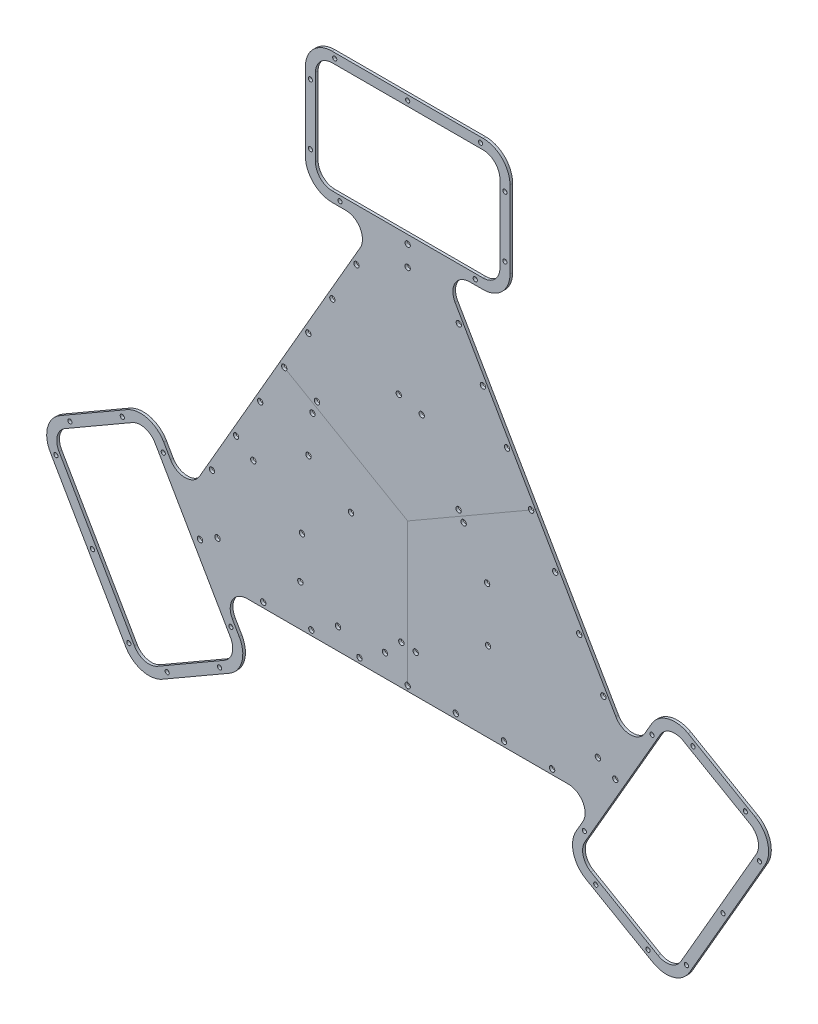
SolidWorks part; units mm, degrees
material "6061 Alloy"
ref_plane "Front Plane" through (0, 0, 0) normal (0, 0, 1) x (1, 0, 0)
ref_plane "Top Plane" through (0, 0, 0) normal (0, 1, 0) x (1, 0, 0)
ref_plane "Right Plane" through (0, 0, 0) normal (1, 0, 0) x (0, 0, -1)
sketch "Master" plane through (0, 0, 0) normal (0, 0, 1) x (1, 0, 0)
  line L0 (0, 0) -> (-128.1513, -73.9882) construction
  line L1 (0, 175.9764) -> (-152.4, -87.9882) construction
  line L2 (-152.4, -87.9882) -> (152.4, -87.9882) construction
  line L3 (152.4, -87.9882) -> (0, 175.9764) construction
  line L4 (0, 0) -> (128.1513, -73.9882) construction
  line L5 (0, 0) -> (0, 147.9764) construction
  line L7 (128.1513, -73.9882) -> (152.4, -87.9882) construction
  line L8 (-128.1513, -73.9882) -> (-152.4, -87.9882) construction
  line L10 (0, 147.9764) -> (0, 175.9764) construction
  line L16 (-16.1658, 147.9764) -> (16.1658, 147.9764)
  line L17 (16.1658, 147.9764) -> (136.2342, -59.9882)
  line L18 (-16.1658, 147.9764) -> (-136.2342, -59.9882)
  line L19 (136.2342, -59.9882) -> (128.1513, -73.9882)
  line L23 (128.1513, -73.9882) -> (120.0684, -87.9882)
  line L24 (120.0684, -87.9882) -> (-120.0684, -87.9882)
  line L25 (-120.0684, -87.9882) -> (-128.1513, -73.9882)
  line L29 (-128.1513, -73.9882) -> (-136.2342, -59.9882)
  circle A0 centre (0, 0) radius 175.9764 construction
  circle A1 centre (-123.8212, -71.4882) radius 5 construction
  circle A2 centre (-123.8212, -71.4882) radius 1.6 construction
  circle A3 centre (0, 142.9764) radius 5 construction
  circle A4 centre (123.8212, -71.4882) radius 5 construction
  circle A5 centre (123.8212, -71.4882) radius 1.6 construction
  circle A6 centre (0, 142.9764) radius 1.6 construction
  circle A11 centre (0, 130.9764) radius 5 construction
  circle A12 centre (0, 130.9764) radius 1.6 construction
  circle A13 centre (113.4289, -65.4882) radius 5 construction
  circle A14 centre (113.4289, -65.4882) radius 1.6 construction
  circle A15 centre (-113.4289, -65.4882) radius 5 construction
  circle A16 centre (-113.4289, -65.4882) radius 1.6 construction
  dimension "D6" = 3.2
  dimension "D5" = 10
  dimension "D3" = 304.8
  dimension "D7" = 12
  dimension "D8" = 12
  dimension "D9" = 12
  dimension "D1" = 28
extrude "Boss-Extrude2" add sketch "Master" along normal blind 1.6
ref_plane "Left Wheel Axle" through (0, 0, 0) normal (-0.5, -0.866, 0) x (0.866, -0.5, 0)
ref_plane "Right Wheel Axle" through (0, 0, 0) normal (-0.5, 0.866, 0) x (-0.866, -0.5, 0)
ref_plane "Rear Wheel Axle" through (0, 0, 0) normal (1, 0, 0) x (0, 1, 0)
ref_axis "Vertical center axis" through (0, 0, -238.9779) along (0, 0, 1)
sketch "Sketch2" plane through (0, 0, 0) normal (0, 0, 1) x (1, 0, 0)
  line L0 (0, 0) -> (0, 147.9764) construction
  line L1 (-55, 214.0964) -> (-55, 220.0964) construction
  line L2 (-55, 214.0964) -> (55, 214.0964)
  line L3 (-55, 214.0964) -> (-55, 147.9764)
  line L4 (-55, 147.9764) -> (55, 147.9764)
  line L5 (55, 214.0964) -> (55, 147.9764)
  line L6 (-55, 214.0964) -> (55, 147.9764) construction
  line L7 (-55, 147.9764) -> (55, 214.0964) construction
  line L8 (-61, 220.0964) -> (61, 220.0964)
  line L9 (-61, 220.0964) -> (-61, 141.9764)
  line L10 (-61, 141.9764) -> (61, 141.9764)
  line L11 (61, 220.0964) -> (61, 141.9764)
  line L12 (-61, 220.0964) -> (61, 141.9764) construction
  line L13 (-61, 141.9764) -> (61, 220.0964) construction
  line L14 (-55, 214.0964) -> (-61, 214.0964) construction
  line L15 (16.1658, 147.9764) -> (-16.1658, 147.9764) construction
  point P0 (0, 147.9764)
  point P3 (0, 181.0364)
  point P16 (0, 181.0364)
  dimension "D1" = 6
  dimension "D2" = 66.12
  dimension "D3" = 110
extrude "Wheel bumpers" add sketch "Sketch2" along normal up to surface (1.6 mm away) up to face at (0, 0, 1.6)
sketch "Sketch3" plane through (0, 0, 1.6) normal (0, 0, 1) x (1, 0, 0)
  line L0 (0, 220.0964) -> (0, 214.0964) construction
  line L1 (-61, 220.0964) -> (61, 220.0964) construction
  line L2 (-55, 214.0964) -> (55, 214.0964) construction
  line L3 (0, 217.0964) -> (29, 217.0964) construction
  line L4 (61, 220.0964) -> (61, 141.9764) construction
  line L5 (0, 217.0964) -> (-29, 217.0964) construction
  line L6 (-61, 141.9764) -> (-61, 220.0964) construction
  line L7 (-61, 181.0364) -> (-55, 181.0364) construction
  line L8 (-55, 147.9764) -> (-55, 214.0964) construction
  line L9 (55, 181.0364) -> (61, 181.0364) construction
  line L10 (55, 214.0964) -> (55, 147.9764) construction
  line L11 (58, 181.0364) -> (58, 144.9764) construction
  line L13 (58, 181.0364) -> (58, 217.0964) construction
  line L14 (-58, 181.0364) -> (-58, 217.0964) construction
  line L15 (-58, 181.0364) -> (-58, 144.9764) construction
  line L17 (-19.6299, 141.9764) -> (-19.6299, 147.9764) construction
  line L19 (19.6299, 141.9764) -> (19.6299, 147.9764) construction
  line L20 (55, 147.9764) -> (-55, 147.9764) construction
  line L21 (-19.6299, 141.9764) -> (19.6299, 141.9764) construction
  line L22 (-19.6299, 144.9764) -> (-61, 144.9764) construction
  line L23 (19.6299, 144.9764) -> (61, 144.9764) construction
  line L24 (-29, 217.0964) -> (-58, 217.0964) construction
  line L25 (29, 217.0964) -> (58, 217.0964) construction
  circle A0 centre (43.5, 217.0964) radius 1.25
  circle A1 centre (0, 217.0964) radius 1.25
  circle A2 centre (-43.5, 217.0964) radius 1.25
  circle A3 centre (-58, 199.0664) radius 1.25
  circle A4 centre (-58, 163.0064) radius 1.25
  circle A9 centre (58, 199.0664) radius 1.25
  circle A10 centre (58, 163.0064) radius 1.25
  circle A11 centre (-40.315, 144.9764) radius 1.25
  circle A12 centre (40.315, 144.9764) radius 1.25
  point P7 (43.5, 217.0964)
  point P27 (58, 163.0064)
  point P28 (58, 199.0664)
  point P34 (-58, 199.0664)
  point P35 (-58, 163.0064)
  point P66 (-43.5, 217.0964)
  dimension "D1" = 2.5
extrude "Bumper mounting holes" cut sketch "Sketch3" against normal up to next
fillet "Bumper outer fillets" radius 16 4 edges at (-61, 141.9764, 0.8) (-61, 220.0964, 0.8) (61, 220.0964, 0.8) (61, 141.9764, 0.8)
fillet "Bumper inner fillets" radius 10 4 edges at (55, 214.0964, 0.8) (55, 147.9764, 0.8) (-55, 147.9764, 0.8) (-55, 214.0964, 0.8)
pattern_circular "CirPattern3" count 3 every 120 about axis through (0, 0, -238.9779) along (0, 0, 1) of "Wheel bumpers", "Bumper mounting holes", "Bumper outer fillets", "Bumper inner fillets"
fillet "Bumper pocket fillets" radius 10 6 edges at (-19.6299, 141.9764, 0.8) (19.6299, 141.9764, 0.8) (132.7701, -53.9882, 0.8) (113.1402, -87.9882, 0.8) (-132.7701, -53.9882, 0.8) (-113.1402, -87.9882, 0.8)
sketch "Motor mounting holes" plane through (0, 0, 0) normal (0, 0, 1) x (1, 0, 0)
  circle A0 centre (0, 142.9764) radius 1.6
  circle A1 centre (0, 130.9764) radius 1.6
  circle A2 centre (-113.4289, -65.4882) radius 1.6
  circle A3 centre (-123.8212, -71.4882) radius 1.6
  circle A4 centre (113.4289, -65.4882) radius 1.6
  circle A5 centre (123.8212, -71.4882) radius 1.6
  dimension "D1" = 3.2
extrude "Motors" cut sketch "Motor mounting holes" along normal up to next
sketch "Sketch1" plane through (0, 0, 1.6) normal (0, 0, 1) x (1, 0, 0)
  circle A0 centre (-41.5385, -75.2533) radius 1.75 construction
  circle A2 centre (-13.5218, -74.7795) radius 1.75 construction
  circle A3 centre (-13.5218, -74.7795) radius 1.75 construction
  circle A4 centre (-41.5385, -75.2533) radius 1.75 construction
  circle A6 centre (-63.9798, -63.3837) radius 1.75 construction
  circle A7 centre (-63.9798, -63.3837) radius 1.75 construction
  circle A8 centre (-92.0288, -14.8014) radius 1.75 construction
  circle A9 centre (-92.0288, -14.8014) radius 1.75 construction
  circle A10 centre (-59.1198, 4.1986) radius 1.75 construction
  circle A11 centre (-59.1198, 4.1986) radius 1.75 construction
  circle A12 centre (-92.0288, -14.8014) radius 1.75 construction
  circle A13 centre (-59.1198, 4.1986) radius 1.75 construction
  circle A14 centre (-63.0385, -38.0142) radius 1.75 construction
  circle A15 centre (-63.0385, -38.0142) radius 1.75 construction
  circle A16 centre (-92.0288, -14.8014) radius 1.6
  circle A17 centre (-63.0385, -38.0142) radius 1.6
  circle A18 centre (-63.9798, -63.3837) radius 1.6
  circle A19 centre (-41.5385, -75.2533) radius 1.6
  circle A20 centre (-13.5218, -74.7795) radius 1.6
  circle A21 centre (-59.1198, 4.1986) radius 1.6
  dimension "D1" = 3.2
extrude "Extension board" cut sketch "Sketch1" against normal up to next
sketch "Sketch6" plane through (0, 0, 0) normal (0, 0, -1) x (-1, 0, 0)
  circle A0 centre (-86.1542, -84.9882) radius 1.6 construction
  circle A1 centre (-57.4361, -84.9882) radius 1.6 construction
  circle A2 centre (-28.7181, -84.9882) radius 1.6 construction
  circle A3 centre (0, -84.9882) radius 1.6 construction
  circle A4 centre (28.7181, -84.9882) radius 1.6 construction
  circle A5 centre (57.4361, -84.9882) radius 1.6 construction
  circle A6 centre (86.1542, -84.9882) radius 1.6 construction
  circle A7 centre (116.679, -32.1176) radius 1.6 construction
  circle A8 centre (102.32, -7.247) radius 1.6 construction
  circle A9 centre (87.9609, 17.6235) radius 1.6 construction
  circle A10 centre (73.6019, 42.4941) radius 1.6 construction
  circle A11 centre (59.2429, 67.3647) radius 1.6 construction
  circle A12 centre (44.8839, 92.2352) radius 1.6 construction
  circle A13 centre (30.5248, 117.1058) radius 1.6 construction
  circle A14 centre (-30.5248, 117.1058) radius 1.6 construction
  circle A15 centre (-44.8839, 92.2352) radius 1.6 construction
  circle A16 centre (-59.2429, 67.3647) radius 1.6 construction
  circle A17 centre (-73.6019, 42.4941) radius 1.6 construction
  circle A18 centre (-87.9609, 17.6235) radius 1.6 construction
  circle A19 centre (-102.32, -7.2471) radius 1.6 construction
  circle A20 centre (-116.679, -32.1176) radius 1.6 construction
  circle A21 centre (-86.1542, -84.9882) radius 1.6
  circle A22 centre (-57.4361, -84.9882) radius 1.6
  circle A23 centre (-28.7181, -84.9882) radius 1.6
  circle A24 centre (0, -84.9882) radius 1.6
  circle A25 centre (28.7181, -84.9882) radius 1.6
  circle A26 centre (57.4361, -84.9882) radius 1.6
  circle A27 centre (86.1542, -84.9882) radius 1.6
  circle A28 centre (116.679, -32.1176) radius 1.6
  circle A29 centre (102.32, -7.247) radius 1.6
  circle A30 centre (87.9609, 17.6235) radius 1.6
  circle A31 centre (73.6019, 42.4941) radius 1.6
  circle A32 centre (59.2429, 67.3647) radius 1.6
  circle A33 centre (44.8839, 92.2352) radius 1.6
  circle A34 centre (30.5248, 117.1058) radius 1.6
  circle A35 centre (-30.5248, 117.1058) radius 1.6
  circle A36 centre (-44.8839, 92.2352) radius 1.6
  circle A37 centre (-59.2429, 67.3647) radius 1.6
  circle A38 centre (-73.6019, 42.4941) radius 1.6
  circle A39 centre (-87.9609, 17.6235) radius 1.6
  circle A40 centre (-102.32, -7.2471) radius 1.6
  circle A41 centre (-116.679, -32.1176) radius 1.6
extrude "Side bumpers" cut sketch "Sketch6" against normal up to next
sketch "Sketch10" plane through (0, 0, 0) normal (0, 0, 1) x (1, 0, 0)
  line L0 (0, 0) -> (0, -87.9882)
  line L1 (-95.8197, -87.9882) -> (95.8197, -87.9882) construction
  line L2 (0, 0) -> (-76.2, 43.9941)
  line L3 (-28.2902, 126.9764) -> (-124.1098, -38.9882) construction
sketch "Sketch11" plane through (0, 0, 0) normal (0, 0, 1) x (1, 0, 0)
  circle A0 centre (-54.0477, 34.6134) radius 1.4 construction
  circle A1 centre (-56.7439, 27.2833) radius 1.4 construction
  circle A2 centre (-33.7439, -12.5538) radius 1.4 construction
  circle A3 centre (-3.7439, -64.5154) radius 1.4 construction
  circle A4 centre (4.8183, -65.3455) radius 1.4 construction
  circle A5 centre (47.9463, -40.4455) radius 1.4 construction
  circle A6 centre (47.3697, -8.4468) radius 1.4 construction
  circle A7 centre (33.3697, 15.8019) radius 1.4 construction
  circle A8 centre (30.3697, 20.9981) radius 1.4 construction
  circle A9 centre (-5.2905, 62.7634) radius 1.4 construction
  circle A10 centre (8.3697, 59.1032) radius 1.4 construction
  circle A11 centre (-54.0477, 34.6134) radius 1.4 construction
  circle A12 centre (-56.7439, 27.2833) radius 1.4 construction
  circle A13 centre (-33.7439, -12.5538) radius 1.4 construction
  circle A14 centre (-3.7439, -64.5154) radius 1.4 construction
  circle A15 centre (4.8183, -65.3455) radius 1.4 construction
  circle A16 centre (47.9463, -40.4455) radius 1.4 construction
  circle A17 centre (47.3697, -8.4468) radius 1.4 construction
  circle A18 centre (33.3697, 15.8019) radius 1.4 construction
  circle A19 centre (30.3697, 20.9981) radius 1.4 construction
  circle A20 centre (-5.2905, 62.7634) radius 1.4 construction
  circle A21 centre (8.3697, 59.1032) radius 1.4 construction
  circle A22 centre (-54.0477, 34.6134) radius 1.6
  circle A23 centre (-56.7439, 27.2833) radius 1.6
  circle A24 centre (-5.2905, 62.7634) radius 1.6
  circle A25 centre (8.3697, 59.1032) radius 1.6
  circle A26 centre (30.3697, 20.9981) radius 1.6
  circle A27 centre (33.3697, 15.8019) radius 1.6
  circle A28 centre (47.3697, -8.4468) radius 1.6
  circle A29 centre (47.9463, -40.4455) radius 1.6
  circle A30 centre (4.8183, -65.3455) radius 1.6
  circle A31 centre (-3.7439, -64.5154) radius 1.6
  circle A32 centre (-33.7439, -12.5538) radius 1.6
  circle A33 centre (-73.6019, 42.4941) radius 1.6 construction
ref_plane "Top" through (0, 0, 1.6) normal (0, 0, 1) x (1, 0, 0)
split "Split1" trim tools "Sketch10" bodies to split 114 resulting bodies 117 118
split "Split2" trim tools "Right Wheel Axle" bodies to split 117 resulting bodies 119 120
extrude "Battery" cut sketch "Sketch11" along normal up to next (1.6 mm away)
equation "\"motor_holder_hole_dist\"=12"
equation "\"D7@Master\"=\"motor_holder_hole_dist\""
equation "\"D8@Master\"=\"motor_holder_hole_dist\""
equation "\"D9@Master\"=\"motor_holder_hole_dist\""
